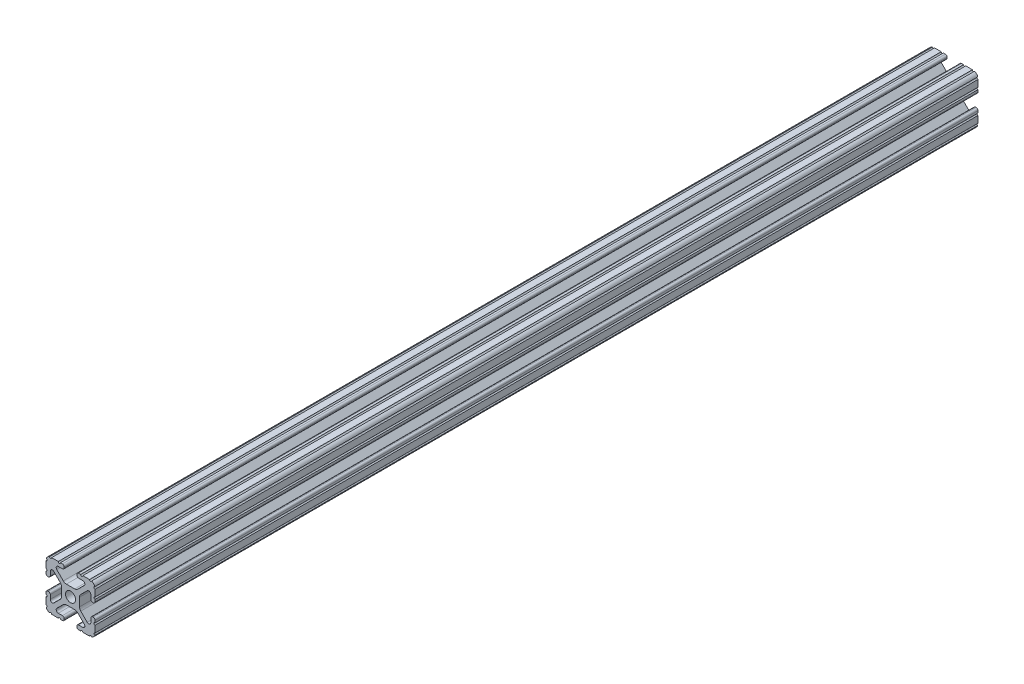
SolidWorks part; units mm, degrees
ref_plane "Front Plane" through (0, 0, 0) normal (0, 0, 1) x (1, 0, 0)
ref_plane "Top Plane" through (0, 0, 0) normal (0, 1, 0) x (1, 0, 0)
ref_plane "Right Plane" through (0, 0, 0) normal (1, 0, 0) x (0, 0, -1)
sketch "Sketch2" plane through (0, 0, 0) normal (0, 0, 1) x (1, 0, 0)
  line L0 (0, 12.7) -> (0, -12.7) construction
  line L1 (-12.7, 0) -> (12.7, 0) construction
  line L2 (3.2512, -12.7) -> (12.7, -12.7)
  line L3 (12.7, -12.7) -> (12.7, -3.2512)
  line L4 (3.2512, -12.7) -> (3.2512, -10.4902)
  line L5 (3.2512, -10.4902) -> (8.9276, -10.4902)
  line L6 (8.9276, -10.4902) -> (3.0856, -4.6482)
  line L7 (0, 0) -> (12.7, -12.7) construction
  line L8 (12.7, -3.2512) -> (10.4902, -3.2512)
  line L9 (10.4902, -3.2512) -> (10.4902, -8.9276)
  line L10 (10.4902, -8.9276) -> (4.6482, -3.0856)
  circle A0 centre (0, 0) radius 2.6035
  arc A1 (6.3485, -10.4902) -> (7.1039, -8.6665) centre (6.3485, -9.4219) ccw construction
  point P8 (0, -4.6482)
  dimension "Center Hole Diameter" = 5.207
  dimension "Rail Height" = 25.4
  dimension "Rail Width" = 25.4
  dimension "T-Slot Width" = 6.5024
  dimension "Slot Inner Width" = 14.8336
  dimension "Thickness" = 2.2098
  dimension "Slot Depth" = 5.842
  dimension "D1" = 2.2098
sketch "Sketch3" plane through (0, 0, 0) normal (1, 0, 0) x (0, 0, -1)
  line L0 (-228.6, -12.7) -> (228.6, -12.7) construction
  line L1 (-205.74, 0) -> (205.74, 0) construction
  dimension "Length" = 457.2
  dimension "D1" = 411.48
sketch "Sketch4" plane through (0, 0, 0) normal (0, 0, 1) x (1, 0, 0)
  line L0 (4.1904, -12.7) -> (10.1173, -12.7)
  line L1 (3.2512, -12.7) -> (12.7, -12.7) construction
  line L2 (3.2512, -12.7) -> (3.2512, -10.4902) construction
  line L3 (3.2512, -10.4902) -> (8.9276, -10.4902) construction
  line L4 (3.2512, -11.4294) -> (3.2512, -11.7608)
  line L5 (4.1904, -10.4902) -> (6.3485, -10.4902)
  line L6 (0, -4.6482) -> (2.164, -4.6482)
  line L7 (8.9276, -10.4902) -> (3.0856, -4.6482) construction
  line L8 (3.7373, -5.2999) -> (7.1039, -8.6665)
  line L9 (12.7, -12.7) -> (12.7, -3.2512) construction
  line L10 (10.4902, -8.9276) -> (4.6482, -3.0856) construction
  line L11 (10.4902, -3.2512) -> (10.4902, -8.9276) construction
  line L12 (10.4902, -6.3485) -> (10.4902, -4.1904)
  line L13 (12.7, -3.2512) -> (10.4902, -3.2512) construction
  line L14 (11.4294, -3.2512) -> (11.7608, -3.2512)
  line L15 (12.7, -4.1904) -> (12.7, -10.1173)
  line L16 (8.6665, -7.1039) -> (5.2999, -3.7373)
  line L17 (4.6482, 0) -> (4.6482, -2.164)
  line L18 (-12.7, 0) -> (12.7, 0) construction
  line L19 (0, -4.6482) -> (0, -2.6035)
  line L20 (0, 12.7) -> (0, -12.7) construction
  line L21 (4.6482, 0) -> (2.6035, 0)
  arc A0 (3.2512, -11.7608) -> (4.1904, -12.7) centre (4.1904, -11.7608) ccw
  arc A2 (3.2512, -11.4294) -> (4.1904, -10.4902) centre (4.1904, -11.4294) cw
  arc A3 (6.3485, -10.4902) -> (7.1039, -8.6665) centre (6.3485, -9.4219) ccw
  arc A4 (2.164, -4.6482) -> (3.7373, -5.2999) centre (2.164, -6.8732) cw
  arc A5 (10.1173, -12.7) -> (12.7, -10.1173) centre (10.1173, -10.1173) ccw
  arc A6 (8.6665, -7.1039) -> (10.4902, -6.3485) centre (9.4219, -6.3485) ccw
  arc A7 (10.4902, -4.1904) -> (11.4294, -3.2512) centre (11.4294, -4.1904) cw
  arc A8 (11.7608, -3.2512) -> (12.7, -4.1904) centre (11.7608, -4.1904) cw
  arc A9 (5.2999, -3.7373) -> (4.6482, -2.164) centre (6.8732, -2.164) cw
  circle A10 centre (0, 0) radius 2.6035 construction
  arc A11 (0, -2.6035) -> (2.6035, 0) centre (0, 0) ccw
  dimension "D1" = 2.5827
  dimension "D2" = 2.225
  dimension "D3" = 0.9392
extrude "Boss-Extrude1" add sketch "Sketch4" along normal mid plane 457.2
sketch "Sketch5" plane through (0, 0, 0) normal (0, 0, 1) x (1, 0, 0)
  line L0 (3.2512, -12.7) -> (12.7, -12.7) construction
  line L1 (4.1904, -10.4902) -> (6.3485, -10.4902) construction
  line L3 (0, 0) -> (12.7, -12.7) construction
  line L4 (6.3485, -10.4902) -> (6.3485, -12.7) construction
  line L5 (8.9276, -10.4902) -> (3.0856, -4.6482) construction
  circle A0 centre (10.3562, -12.7) radius 0.5524
  circle A1 centre (5.796, -12.7) radius 0.5524
  circle A2 centre (12.7, -10.3562) radius 0.5524
  circle A3 centre (12.7, -5.796) radius 0.5524
  point P10 (5.2694, -10.4902)
  point P12 (9.4219, -6.3485)
  dimension "D1" = 1.1049
extrude "Cut-Extrude1" cut sketch "Sketch5" against normal through all both and the other way through all
mirror "Mirror1" about plane through (0, 0, 0) normal (1, 0, 0) of bodies 137 134
mirror "Mirror2" about plane through (0, 0, 0) normal (0, 1, 0) of bodies 135
equation "\"D1@Boss-Extrude1\"=\"Length@Sketch3\""
equation "\"D1@Sketch2\"=\"Thickness@Sketch2\""
equation "\"D2@Sketch4\"=\"Slot Inner Width@Sketch2\"*0.15"
equation "\"D1@Sketch4\"=\"D3@Sketch4\"*2.75"
equation "\"D3@Sketch4\"=\"Thickness@Sketch2\"*0.425"
equation "\"D1@Sketch5\"=\"Thickness@Sketch2\"*0.5"
equation "\"D1@Sketch3\"=\"Length@Sketch3\"*0.9"
